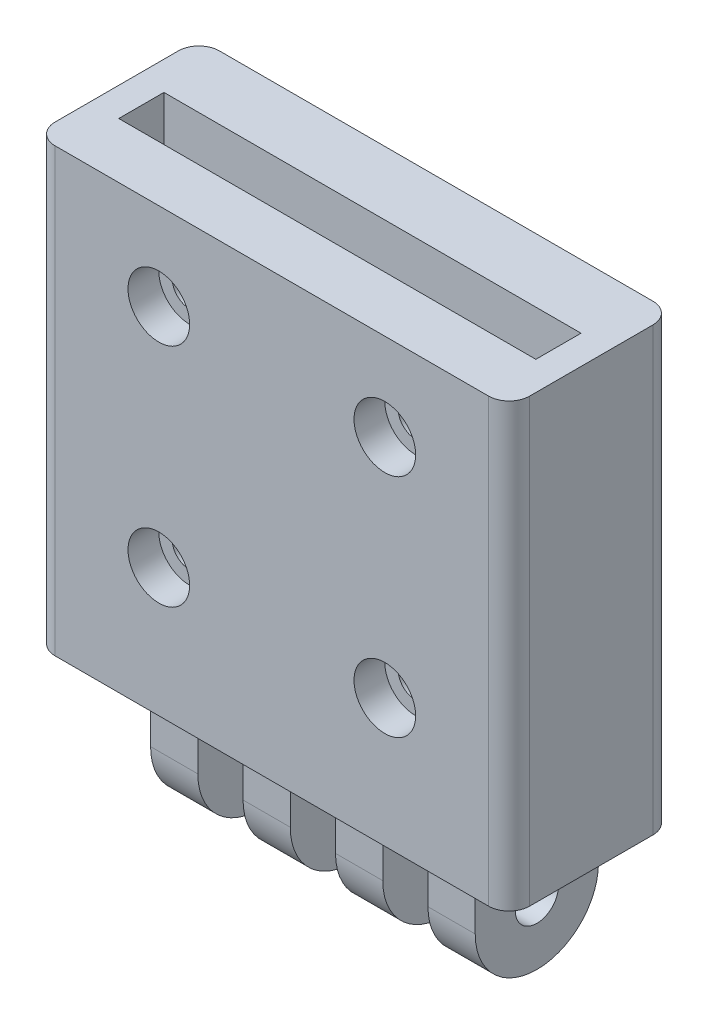
SolidWorks part; units mm, degrees
ref_plane "Front Plane" through (0, 0, 0) normal (0, 0, 1) x (1, 0, 0)
ref_plane "Top Plane" through (0, 0, 0) normal (0, 1, 0) x (1, 0, 0)
ref_plane "Right Plane" through (0, 0, 0) normal (1, 0, 0) x (0, 0, -1)
sketch "Sketch1" plane through (0, 0, 0) normal (0, 1, 0) x (1, 0, 0)
  line L1 (23.1, 8) -> (-23.1, 8)
  line L2 (23.1, 8) -> (23.1, -8)
  line L3 (23.1, -8) -> (-23.1, -8)
  line L4 (-23.1, 8) -> (-23.1, -8)
  line L5 (23.1, 8) -> (-23.1, -8) construction
  line L6 (23.1, -8) -> (-23.1, 8) construction
  point P0 (0, 0)
  dimension "D1" = 16
  dimension "D2" = 46.2
extrude "Boss-Extrude1" add sketch "Sketch1" along normal blind 43
sketch "Sketch2" plane through (0, 0, 0) normal (0, -1, 0) x (1, 0, 0)
  line L0 (23.1, -8) -> (-23.1, -8) construction
  line L1 (15.8, -8) -> (11.2, -8)
  line L2 (15.8, -8) -> (15.8, 4)
  line L3 (15.8, 4) -> (11.2, 4)
  line L4 (11.2, -8) -> (11.2, 4)
  line L5 (13.5, 8) -> (13.5, -8) construction
  line L6 (15.8, -2) -> (11.2, -2) construction
  point P272 (13.5, -2)
  dimension "D1" = 12
  dimension "D2" = 4.6
extrude "Boss-Extrude2" add sketch "Sketch2" along normal blind 7
sketch "Sketch8" plane through (15.8, 0, 0) normal (1, 0, 0) x (0, 0, -1)
  line L0 (8, -7) -> (-4, -7) construction
  line L1 (8, -7) -> (8, 0) construction
  circle A0 centre (2, -7) radius 6
  point P2 (0, 0)
  dimension "D1" = 12
extrude "Boss-Extrude3" add sketch "Sketch8" against normal up to surface (4.6 mm away) up to face at (11.2, -3.5, -2)
pattern_linear "LPattern1" count 4 spacing 9 along (-1, 0, 0) of "Boss-Extrude2", "Boss-Extrude3"
sketch "Sketch4" plane through (15.8, 0, 0) normal (1, 0, 0) x (0, 0, -1)
  circle A0 centre (2, -7) radius 2.1
  arc A2 (-4, -7) -> (8, -7) centre (2, -7) ccw construction
  dimension "D1" = 4.2
  dimension "D2" = 0
extrude "Cut-Extrude1" cut sketch "Sketch4" against normal through all
sketch "Sketch6" plane through (0, 43, 0) normal (0, 1, 0) x (1, 0, 0)
  line L0 (-23.1, -8) -> (23.1, -8) construction
  line L1 (20.3, -2.6) -> (-20.3, -2.6)
  line L2 (20.3, -2.6) -> (20.3, 1.8)
  line L3 (20.3, 1.8) -> (-20.3, 1.8)
  line L4 (-20.3, -2.6) -> (-20.3, 1.8)
  line L5 (20.3, -2.6) -> (-20.3, 1.8) construction
  line L6 (20.3, 1.8) -> (-20.3, -2.6) construction
  line L7 (-23.1, 8) -> (-23.1, -8) construction
  line L9 (23.1, 8) -> (-23.1, 8) construction
  point P0 (0, -0.4)
  dimension "D1" = 5.4
  dimension "D2" = 2.8
  dimension "D3" = 6.2
extrude "Cut-Extrude2" cut sketch "Sketch6" against normal blind 40
sketch "Sketch9" plane through (0, 0, 8) normal (0, 0, 1) x (1, 0, 0)
  line L0 (20, 43) -> (20, 0) construction
  line L1 (-23.1, 43) -> (23.1, 43) construction
  line L2 (-23.1, 0) -> (23.1, 0) construction
  line L3 (-20, 43) -> (-20, 0) construction
  line L4 (-23.1, 0) -> (23.1, 0) construction
  line L5 (23.1, 3) -> (-23.1, 3) construction
  line L6 (23.1, 43) -> (23.1, 0) construction
  line L7 (-23.1, 43) -> (-23.1, 0) construction
  line L8 (0, 3) -> (0, 43) construction
  circle A0 centre (11, 12.5) radius 1.7
  circle A1 centre (-11, 12.5) radius 1.7
  circle A2 centre (11, 34.5) radius 1.7
  circle A3 centre (-11, 34.5) radius 1.7
  dimension "D8" = 3.4
  dimension "D1" = 40
  dimension "D2" = 40
  dimension "D3" = 9
  dimension "D4" = 8.5
  dimension "D5" = 9
  dimension "D6" = 9.5
  dimension "D7" = 20
extrude "Cut-Extrude3" cut sketch "Sketch9" against normal through all
fillet "Fillet2" radius 2 4 edges at (23.1, 21.5, -8) (-23.1, 21.5, -8) (-23.1, 21.5, 8) (23.1, 21.5, 8)
sketch "Sketch10" plane through (0, 0, -8) normal (0, 0, -1) x (-1, 0, 0)
  line L0 (12.5877, 9.75) -> (9.4123, 9.75)
  line L1 (9.4123, 9.75) -> (7.8246, 12.5)
  line L2 (7.8246, 12.5) -> (9.4123, 15.25)
  line L3 (9.4123, 15.25) -> (12.5877, 15.25)
  line L4 (12.5877, 15.25) -> (14.1754, 12.5)
  line L5 (14.1754, 12.5) -> (12.5877, 9.75)
  line L6 (12.5877, 9.75) -> (9.4123, 15.25) construction
  line L7 (14.1754, 12.5) -> (7.8246, 12.5) construction
  line L8 (12.5877, 15.25) -> (9.4123, 9.75) construction
  circle A0 centre (11, 12.5) radius 1.7 construction
  point P5 (11, 12.5)
  dimension "D1" = 60
  dimension "D2" = 5.5
extrude "Cut-Extrude4" cut sketch "Sketch10" against normal blind 4
pattern_linear "LPattern2" count 2 spacing 22 along (0, 1, 0) count 2 spacing 22 along (1, 0, 0) of "Cut-Extrude4"
sketch "Sketch11" plane through (0, 0, 8) normal (0, 0, 1) x (1, 0, 0)
  circle A2 centre (11, 12.5) radius 3
  circle A3 centre (-11, 12.5) radius 3
  circle A4 centre (-11, 34.5) radius 3
  circle A5 centre (11, 34.5) radius 3
  dimension "D1" = 6
extrude "Cut-Extrude5" cut sketch "Sketch11" against normal blind 3
